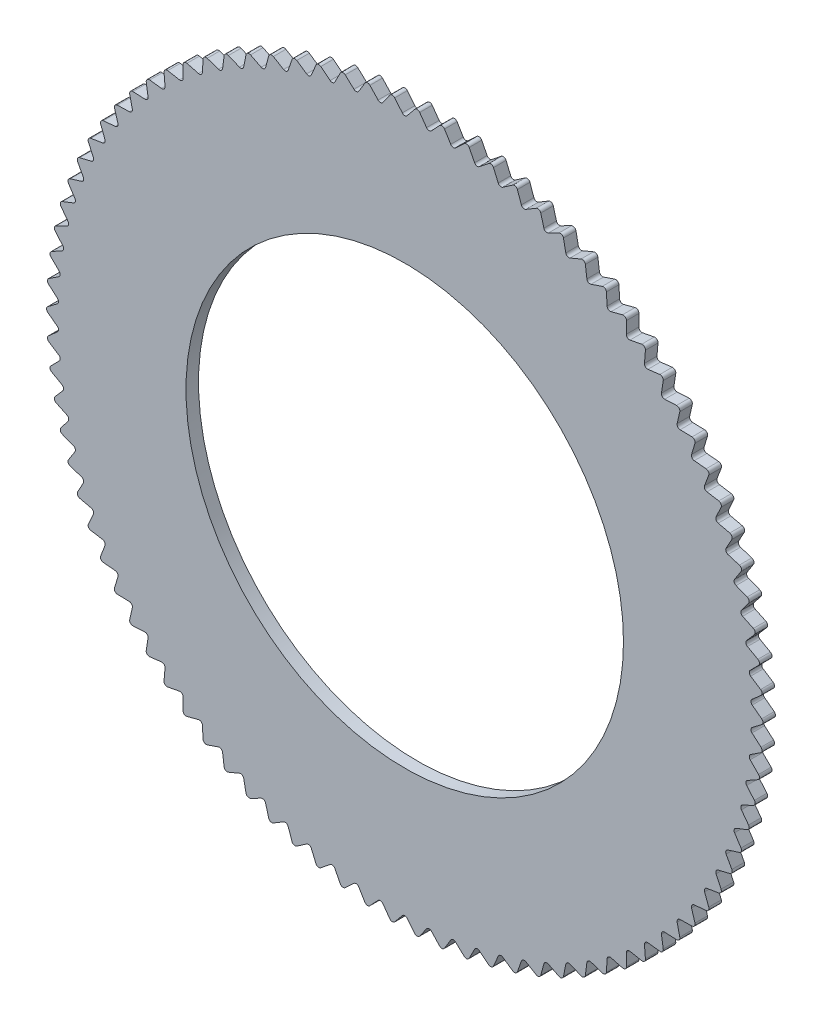
SolidWorks part; units mm, degrees
ref_plane "Front Plane" through (0, 0, 0) normal (0, 0, 1) x (1, 0, 0)
ref_plane "Top Plane" through (0, 0, 0) normal (0, 1, 0) x (1, 0, 0)
ref_plane "Right Plane" through (0, 0, 0) normal (1, 0, 0) x (0, 0, -1)
sketch "Sketch1" plane through (0, 0, 0) normal (0, 0, 1) x (1, 0, 0)
  line L0 (-7.7262, 221.25) -> (7.7262, 221.25) construction
  line L1 (0, 0) -> (0, 221.25) construction
  line L2 (0, 221.25) -> (0, 228.75) construction
  line L5 (-1.5486, 221.9844) -> (-6.3649, 227.8775)
  line L6 (0, 228.75) -> (0, 59.7644) construction
  line L7 (1.5486, 221.9844) -> (6.3649, 227.8775)
  line L8 (0, 0) -> (-7.9833, 228.6107) construction
  line L9 (0, 0) -> (7.9833, 228.6107) construction
  circle A2 centre (0, 0) radius 221.25 construction
  arc A4 (-7.8524, 224.8629) -> (7.8524, 224.8629) centre (0, 0) ccw construction
  circle A5 centre (0, 0) radius 228.75 construction
  arc A6 (-1.5486, 221.9844) -> (1.5486, 221.9844) centre (0, 223.25) ccw
  arc A7 (-6.3649, 227.8775) -> (-7.9833, 228.6107) centre (-7.9135, 226.6119) ccw
  arc A8 (6.3649, 227.8775) -> (7.9833, 228.6107) centre (7.9135, 226.6119) cw
  arc A9 (7.8524, 224.8629) -> (-7.8524, 224.8629) centre (0, 0) ccw construction
  point P13 (7.8524, 224.8629)
  point P18 (-7.8524, 224.8629)
  point P23 (-7.8524, 224.8629)
  dimension "D1" = 442.5
  dimension "D4" = 450
  dimension "D3" = 457.5
  dimension "D2" = 2
  dimension "D5" = 15.708
sketch "Sketch2" plane through (0, 0, 0) normal (0, 0, 1) x (1, 0, 0)
  circle A0 centre (0, 0) radius 228.75
  circle A1 centre (0, 0) radius 228.75 construction
extrude "Boss-Extrude1" add sketch "Sketch2" along normal blind 8
sketch "Sketch4" plane through (0, 0, 8) normal (0, 0, 1) x (1, 0, 0)
  line L0 (1.5486, 221.9844) -> (6.3649, 227.8775) construction
  line L1 (-1.5486, 221.9844) -> (-6.3649, 227.8775) construction
  line L2 (1.5486, 221.9844) -> (6.3649, 227.8775)
  line L3 (-1.5486, 221.9844) -> (-6.3649, 227.8775)
  arc A0 (7.9833, 228.6107) -> (6.3649, 227.8775) centre (7.9135, 226.6119) ccw construction
  arc A1 (-1.5486, 221.9844) -> (1.5486, 221.9844) centre (0, 223.25) ccw construction
  arc A2 (-6.3649, 227.8775) -> (-7.9833, 228.6107) centre (-7.9135, 226.6119) ccw construction
  arc A3 (7.9833, 228.6107) -> (6.3649, 227.8775) centre (7.9135, 226.6119) ccw
  arc A4 (-1.5486, 221.9844) -> (1.5486, 221.9844) centre (0, 223.25) ccw
  arc A5 (-6.3649, 227.8775) -> (-7.9833, 228.6107) centre (-7.9135, 226.6119) ccw
  circle A7 centre (0, 0) radius 228.75
  circle A8 centre (0, 0) radius 228.75
  circle M2 centre (0, 0) radius 228.75
  dimension "D1" = 0
extrude "Cut-Extrude3" cut sketch "Sketch4" against normal blind 20 contours A5 L3 A4 L2 A3 M2 region at (0, 225.9622, 8)
ref_axis "Axis1" through (0, 0, 0) along (0, 0, 1)
pattern_circular "CirPattern1" count 90 over 360 about axis through (0, 0, 0) along (0, 0, 1) of "Cut-Extrude3"
sketch "Sketch5" plane through (0, 0, 8) normal (0, 0, 1) x (1, 0, 0)
  circle A0 centre (0, 0) radius 139.7
  dimension "D1" = 279.4
extrude "Cut-Extrude4" cut sketch "Sketch5" against normal through all
equation "\"pitch diameter\" = 450"
equation "\"OD\"= \"pitch diameter\" + ( \"addendum\" )"
equation "\"ID\"= \"pitch diameter\" - ( \"addendum\" )"
equation "\"module\"= 5"
equation "\"number of teeth\"= \"pitch diameter\" / \"module\""
equation "\"reference pitch\"= ( \"pitch diameter\" * pi ) / \"number of teeth\""
equation "\"D1@Sketch1\"=\"ID\""
equation "\"D4@Sketch1\"=\"pitch diameter\""
equation "\"D3@Sketch1\"=\"OD\""
equation "\"addendum\"= \"module\" * 1.5"
equation "\"D5@Sketch1\"=\"reference pitch\""
equation "\"D1@CirPattern1\"=\"number of teeth\""
